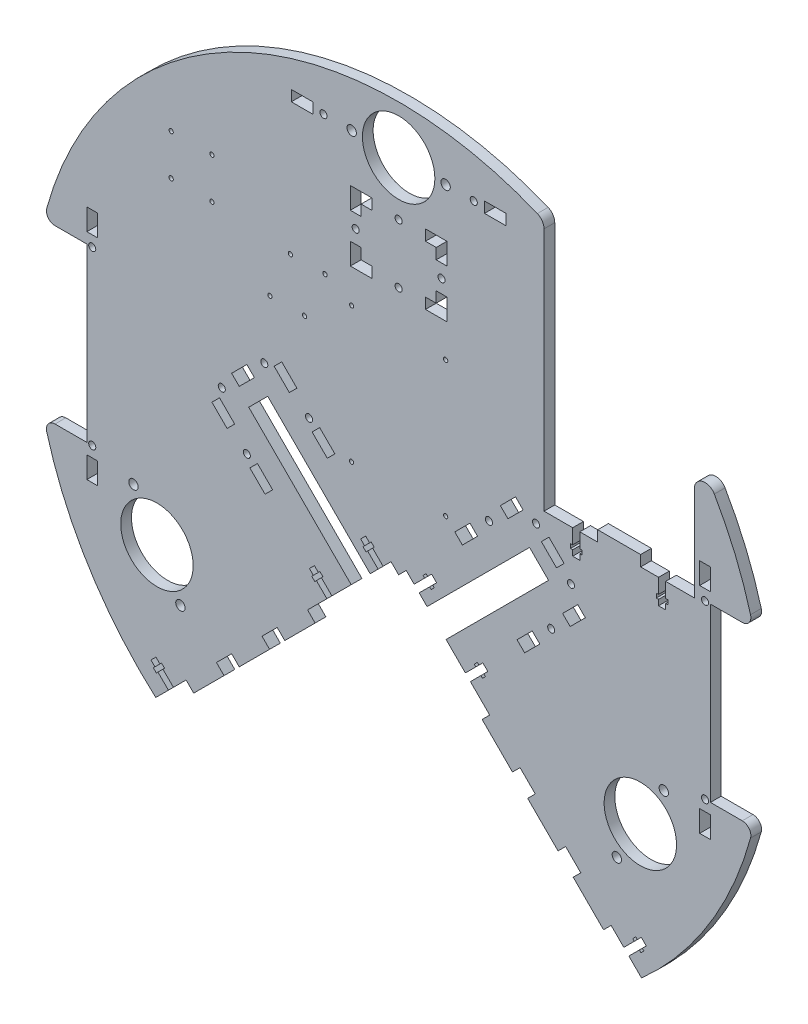
SolidWorks part; units mm, degrees
ref_plane "Front Plane" through (0, 0, 0) normal (0, 0, 1) x (1, 0, 0)
ref_plane "Top Plane" through (0, 0, 0) normal (0, 1, 0) x (1, 0, 0)
ref_plane "Right Plane" through (0, 0, 0) normal (1, 0, 0) x (0, 0, -1)
sketch "Sketch1" plane through (0, 0, 0) normal (0, 0, 1) x (1, 0, 0)
  circle A0 centre (0, 0) radius 215.9
  dimension "D1" = 431.8
extrude "Base Plate Extrusion" add sketch "Sketch1" along normal blind 6.35
sketch "Sketch2" plane through (0, 0, 6.35) normal (0, 0, 1) x (1, 0, 0)
  line L0 (0, 0) -> (0, -230.9791) construction
  line L1 (0, -17.4608) -> (143.6841, -161.1449)
  line L2 (0, -17.4608) -> (-143.6841, -161.1449)
  circle A1 centre (0, 0) radius 215.9 construction
  arc A2 (143.6841, -161.1449) -> (-143.6841, -161.1449) centre (0, 0) cw
  dimension "D1" = 90
  dimension "D2" = 203.2
extrude "V Funnel Cut" cut sketch "Sketch2" against normal through all
sketch "Sketch3" plane through (0, 0, 6.35) normal (0, 0, 1) x (1, 0, 0)
  line L0 (0, 0) -> (251.7982, 0) construction
  line L1 (209.8384, 50.8) -> (184.4384, 50.8)
  line L2 (209.8384, 50.8) -> (209.8384, -50.8)
  line L3 (209.8384, -50.8) -> (184.4384, -50.8)
  line L4 (184.4384, 50.8) -> (184.4384, -50.8)
  arc A0 (143.6841, -161.1449) -> (-143.6841, -161.1449) centre (0, 0) ccw construction
  arc A1 (209.8384, 50.8) -> (209.8384, -50.8) centre (0, 0) cw
  arc M7 (143.6841, -161.1449) -> (-143.6841, -161.1449) centre (0, 0) ccw
  dimension "D1" = 25.4
  dimension "D2" = 101.6
extrude "Wheel Track Cut" cut sketch "Sketch3" against normal through all contours L2 L0 A1 | L4 L0 L2 L1 | L0 L4 L3 L2 | L0 L2 M7 region at (197.1384, 25.4, 6.35) region at (197.1384, -25.4, 6.35) region at (212.266, 19.0862, 6.35) region at (212.266, -19.0862, 6.35)
mirror "Wheel Track Cut Mirror" about plane through (0, 0, 0) normal (1, 0, 0) of "Wheel Track Cut"
sketch "Sketch4" plane through (0, 0, 6.35) normal (0, 0, 1) x (1, 0, 0)
  line L0 (88.68, 15.0926) -> (77.4547, 26.3179)
  line L1 (88.68, 15.0926) -> (28.0633, -45.5241)
  line L2 (77.4547, 26.3179) -> (16.838, -34.2988)
  line L3 (28.0633, -45.5241) -> (16.838, -34.2988)
  line L4 (84.3174, 21.9553) -> (56.956, -5.4061) construction
  line L5 (65.1069, -1.7454) -> (69.5826, 2.7303) construction
  line L6 (65.0924, 7.2204) -> (60.6167, 2.7447) construction
  line L7 (143.6841, -161.1449) -> (0, -17.4608) construction
  dimension "D1" = 15.875
  dimension "D2" = 85.725
extrude "Silo Picker Clearance" cut sketch "Sketch4" against normal through all
sketch "Sketch5" plane through (0, 0, 6.35) normal (0, 0, 1) x (1, 0, 0)
  line L0 (-4.4901, -21.951) -> (0, -17.4608)
  line L1 (-4.4901, -21.951) -> (0, -26.4411)
  line L2 (0, -17.4608) -> (4.4901, -21.951)
  line L3 (0, -26.4411) -> (4.4901, -21.951)
  line L4 (0, -17.4608) -> (-143.6841, -161.1449) construction
  line L6 (4.4901, -21.951) -> (0, -26.4411) construction
  dimension "D1" = 6.35
extrude "V Funnel Corner" add sketch "Sketch5" against normal up to surface (6.35 mm away) up to face at (14.0691, -14.8765, 0)
mirror "Dump Picker Clearance" about plane through (0, 0, 0) normal (1, 0, 0) of "Silo Picker Clearance"
sketch "Sketch6" plane through (8.7304, -8.7304, 0) normal (0.7071, -0.7071, 0) x (0, 0, -1)
  line L0 (-6.35, -52.0342) -> (-6.35, -215.5467) construction
  line L1 (-6.35, -190.1467) -> (0, -190.1467)
  line L2 (-6.35, -190.1467) -> (-6.35, -164.7467)
  line L3 (-6.35, -164.7467) -> (0, -164.7467)
  line L4 (0, -190.1467) -> (0, -164.7467)
  line L5 (0, -52.0342) -> (0, -215.5467) construction
  dimension "D1" = 25.4
  dimension "D2" = 25.4
extrude "V Funnel Tab Left" add sketch "Sketch6" along normal blind 6.35
pattern_linear "V Funnel Tab Pattern Left" count 3 spacing 38.1 along (0.7071, 0.7071, 0) of "V Funnel Tab Left"
sketch "Sketch7" plane through (-8.7304, -8.7304, 0) normal (-0.7071, -0.7071, 0) x (0, 0, 1)
  line L0 (6.35, -215.5467) -> (6.35, -52.0342) construction
  line L1 (6.35, -164.7467) -> (0, -164.7467)
  line L2 (6.35, -164.7467) -> (6.35, -190.1467)
  line L3 (6.35, -190.1467) -> (0, -190.1467)
  line L4 (0, -164.7467) -> (0, -190.1467)
  line L5 (0, -215.5467) -> (0, -52.0342) construction
  dimension "D1" = 25.4
  dimension "D2" = 25.4
extrude "V Funnel Tab Right" add sketch "Sketch7" along normal blind 6.35
pattern_linear "V Funnel Tab Pattern Right" count 3 spacing 38.1 along (-0.7071, 0.7071, 0) of "V Funnel Tab Right"
sketch "Sketch8" plane through (0, 0, 0) normal (0, 0, -1) x (-1, 0, 0)
  line L0 (-70.046, -24.645) -> (-79.0263, -15.6648)
  line L1 (-79.0263, -15.6648) -> (-83.5164, -20.1549)
  line L2 (-83.5164, -20.1549) -> (-74.5361, -29.1352)
  line L3 (-74.5361, -29.1352) -> (-70.046, -24.645)
  line L4 (-96.9868, 2.2957) -> (-101.4769, -2.1944)
  line L5 (-101.4769, -2.1944) -> (-110.4572, 6.7859)
  line L6 (-110.4572, 6.7859) -> (-105.967, 11.276)
  line L7 (-105.967, 11.276) -> (-96.9868, 2.2957)
  line L8 (-97.8965, 28.3267) -> (-88.9163, 37.307)
  line L9 (-88.9163, 37.307) -> (-84.4262, 32.8169)
  line L10 (-84.4262, 32.8169) -> (-93.4064, 23.8366)
  line L11 (-93.4064, 23.8366) -> (-97.8965, 28.3267)
  line L12 (-64.6578, 34.6246) -> (-60.1677, 39.1148)
  line L13 (-60.1677, 39.1148) -> (-69.148, 48.095)
  line L14 (-69.148, 48.095) -> (-73.6381, 43.6049)
  line L15 (-73.6381, 43.6049) -> (-64.6578, 34.6246)
  line L16 (-46.6973, 16.6641) -> (-42.2072, 21.1543)
  line L17 (-42.2072, 21.1543) -> (-33.2269, 12.174)
  line L18 (-33.2269, 12.174) -> (-37.7171, 7.6839)
  line L19 (-37.7171, 7.6839) -> (-46.6973, 16.6641)
  line L20 (-105.967, 11.276) -> (-110.4572, 6.7859) construction
  line L21 (-69.148, 48.095) -> (-73.6381, 43.6049) construction
extrude "Silo Arm Tab Holes" cut sketch "Sketch8" against normal blind 6.35
sketch "Sketch10" plane through (0, 0, 0) normal (0, 0, -1) x (-1, 0, 0)
  line L0 (51.1875, 21.1543) -> (42.2072, 12.174)
  line L1 (42.2072, 12.174) -> (37.7171, 16.6641)
  line L2 (37.7171, 16.6641) -> (46.6973, 25.6444)
  line L3 (46.6973, 25.6444) -> (51.1875, 21.1543)
  line L4 (64.6578, 34.6246) -> (60.1677, 39.1148)
  line L5 (60.1677, 39.1148) -> (69.148, 48.095)
  line L6 (69.148, 48.095) -> (73.6381, 43.6049)
  line L7 (73.6381, 43.6049) -> (64.6578, 34.6246)
  line L8 (89.8026, 36.4207) -> (85.3124, 31.9306)
  line L9 (85.3124, 31.9306) -> (94.2927, 22.9503)
  line L10 (94.2927, 22.9503) -> (98.7828, 27.4404)
  line L11 (98.7828, 27.4404) -> (89.8026, 36.4207)
  line L12 (105.967, 11.276) -> (96.9868, 2.2957)
  line L13 (96.9868, 2.2957) -> (101.4769, -2.1944)
  line L14 (101.4769, -2.1944) -> (110.4572, 6.7859)
  line L15 (110.4572, 6.7859) -> (105.967, 11.276)
  line L16 (88.0065, -15.6648) -> (83.5164, -11.1747)
  line L17 (83.5164, -11.1747) -> (74.5361, -20.1549)
  line L18 (74.5361, -20.1549) -> (79.0263, -24.645)
  line L19 (79.0263, -24.645) -> (88.0065, -15.6648)
  line L20 (37.7171, 16.6641) -> (42.2072, 12.174) construction
  line L21 (74.5361, -20.1549) -> (79.0263, -24.645) construction
extrude "Dump Arm Tab Holes" cut sketch "Sketch10" against normal blind 6.35
sketch "Sketch11" plane through (0, 0, 0) normal (0, 0, -1) x (-1, 0, 0)
  line L1 (184.4384, -69.85) -> (178.0884, -69.85)
  line L2 (184.4384, -69.85) -> (184.4384, -57.15)
  line L3 (184.4384, -57.15) -> (178.0884, -57.15)
  line L4 (178.0884, -69.85) -> (178.0884, -57.15)
  line L5 (184.4384, 57.15) -> (178.0884, 57.15)
  line L6 (184.4384, 57.15) -> (184.4384, 69.85)
  line L7 (184.4384, 69.85) -> (178.0884, 69.85)
  line L8 (178.0884, 57.15) -> (178.0884, 69.85)
  line L9 (-178.0884, -69.85) -> (-184.4384, -69.85)
  line L10 (-178.0884, -69.85) -> (-178.0884, -57.15)
  line L11 (-178.0884, -57.15) -> (-184.4384, -57.15)
  line L12 (-184.4384, -69.85) -> (-184.4384, -57.15)
  line L13 (-178.0884, 57.15) -> (-184.4384, 57.15)
  line L14 (-178.0884, 57.15) -> (-178.0884, 69.85)
  line L15 (-178.0884, 69.85) -> (-184.4384, 69.85)
  line L16 (-184.4384, 57.15) -> (-184.4384, 69.85)
extrude "Wheel Support Tab Holes" cut sketch "Sketch11" against normal blind 6.35
sketch "Sketch13" plane through (0, 0, 6.35) normal (0, 0, 1) x (1, 0, 0)
  circle A0 centre (0, 187.325) radius 21.4313
  circle A1 centre (27.7812, 187.325) radius 2.7781
  circle A2 centre (-27.7813, 187.325) radius 2.7781
  dimension "D1" = 42.8625
  dimension "D2" = 5.5562
extrude "Caster Wheel Hole" cut sketch "Sketch13" against normal through all
sketch "Sketch14" plane through (0, 0, 6.35) normal (0, 0, 1) x (1, 0, 0)
  line L0 (184.4384, 48.6664) -> (178.0884, 52.9336) construction
  line L1 (184.4384, 50.8) -> (184.4384, -50.8) construction
  line L2 (178.0884, 48.6664) -> (184.4384, 48.6664) construction
  line L3 (184.4384, 52.9336) -> (178.0884, 48.6664) construction
  line L4 (184.4384, -52.9336) -> (178.0884, -48.6664) construction
  line L5 (184.4384, -48.6664) -> (178.0884, -52.9336) construction
  line L6 (178.0884, -48.6664) -> (184.4384, -48.6664) construction
  circle A0 centre (181.2634, 50.8) radius 2.0955
  circle A1 centre (181.2634, -50.8) radius 2.0955
  dimension "D1" = 4.191
extrude "Wheel Support Hole" cut sketch "Sketch14" against normal through all
mirror "Wheel Support Hole Mirror" about plane through (0, 0, 0) normal (1, 0, 0) of "Wheel Support Hole"
sketch "Sketch15" plane through (0, 0, 6.35) normal (0, 0, 1) x (1, 0, 0)
  line L0 (-134.7038, -152.1647) -> (-152.6084, -134.2601) construction
  line L1 (-125.7236, -143.1844) -> (-143.6841, -161.1449) construction
  line L2 (-40.9724, -58.4333) -> (-60.7132, -38.6924) construction
  line L3 (-28.0633, -45.5241) -> (-53.8815, -71.3424) construction
  line L4 (-10.6641, -28.1249) -> (-27.2834, -11.5055) construction
  line L5 (-4.4901, -21.951) -> (-16.838, -34.2988) construction
  line B0 (-136.1856, -153.6464) -> (-133.2221, -150.6829)
  line B1 (-141.2145, -142.6905) -> (-140.2716, -141.7476)
  line B2 (-140.2716, -141.7476) -> (-138.4755, -143.5436)
  line B3 (-138.4755, -143.5436) -> (-139.4185, -144.4866)
  line B4 (-139.4185, -144.4866) -> (-133.2221, -150.6829)
  line B5 (-141.2145, -142.6905) -> (-143.5494, -140.3556)
  line B6 (-143.5494, -140.3556) -> (-146.5129, -143.3191)
  line B7 (-144.178, -145.654) -> (-146.5129, -143.3191)
  line B8 (-142.382, -147.45) -> (-136.1856, -153.6464)
  line B9 (-143.3249, -148.393) -> (-142.382, -147.45)
  line B10 (-145.1209, -146.5969) -> (-143.3249, -148.393)
  line B11 (-144.178, -145.654) -> (-145.1209, -146.5969)
  line B12 (-42.4542, -59.915) -> (-39.4907, -56.9515)
  line B13 (-47.4831, -48.9591) -> (-46.5402, -48.0162)
  line B14 (-46.5402, -48.0162) -> (-44.7441, -49.8122)
  line B15 (-44.7441, -49.8122) -> (-45.6871, -50.7551)
  line B16 (-45.6871, -50.7551) -> (-39.4907, -56.9515)
  line B17 (-47.4831, -48.9591) -> (-49.818, -46.6242)
  line B18 (-49.818, -46.6242) -> (-52.7815, -49.5877)
  line B19 (-50.4466, -51.9226) -> (-52.7815, -49.5877)
  line B20 (-48.6505, -53.7186) -> (-42.4542, -59.915)
  line B21 (-49.5935, -54.6615) -> (-48.6505, -53.7186)
  line B22 (-51.3895, -52.8655) -> (-49.5935, -54.6615)
  line B23 (-50.4466, -51.9226) -> (-51.3895, -52.8655)
  line B24 (-12.1458, -29.6066) -> (-9.1823, -26.6431)
  line B25 (-17.1747, -18.6507) -> (-16.2318, -17.7078)
  line B26 (-16.2318, -17.7078) -> (-14.4358, -19.5038)
  line B27 (-14.4358, -19.5038) -> (-15.3787, -20.4468)
  line B28 (-15.3787, -20.4468) -> (-9.1823, -26.6431)
  line B29 (-17.1747, -18.6507) -> (-19.5096, -16.3159)
  line B30 (-19.5096, -16.3159) -> (-22.4731, -19.2793)
  line B31 (-20.1382, -21.6142) -> (-22.4731, -19.2793)
  line B32 (-18.3422, -23.4103) -> (-12.1458, -29.6066)
  line B33 (-19.2851, -24.3532) -> (-18.3422, -23.4103)
  line B34 (-21.0812, -22.5571) -> (-19.2851, -24.3532)
  line B35 (-20.1382, -21.6142) -> (-21.0812, -22.5571)
sketch_block_instance "TSlot-1"
sketch_block "TSlot" parameters "D1"=3.302, "D2"=2.54, "D3"=3.175, "D4"=8.763, "D5"=1.3462
sketch_block_instance "TSlot-3"
sketch_block_instance "TSlot-4"
extrude "V Funnel T Slot Cut Out" cut sketch "Sketch15" against normal through all
mirror "V Funnel T Slot Cut Out Mirror" about plane through (0, 0, 0) normal (1, 0, 0) of "V Funnel T Slot Cut Out"
sketch "Sketch19" plane through (0, 0, 6.35) normal (0, 0, 1) x (1, 0, 0)
  line L0 (46.5836, 190.5) -> (42.3164, 184.15) construction
  line L1 (46.5836, 184.15) -> (42.3164, 190.5) construction
  line L2 (-42.3164, 190.5) -> (-46.5836, 184.15) construction
  line L3 (-42.3164, 184.15) -> (-46.5836, 190.5) construction
  circle A0 centre (44.45, 187.325) radius 2.0955
  circle A1 centre (-44.45, 187.325) radius 2.0955
  dimension "D1" = 4.191
extrude "Switch Plate Holes" cut sketch "Sketch19" against normal through all
sketch "Sketch20" plane through (0, 0, 0) normal (0, 0, -1) x (-1, 0, 0)
  line L1 (-50.8, 184.15) -> (-63.5, 184.15)
  line L2 (-50.8, 184.15) -> (-50.8, 190.5)
  line L3 (-50.8, 190.5) -> (-63.5, 190.5)
  line L4 (-63.5, 184.15) -> (-63.5, 190.5)
  line L5 (63.5, 184.15) -> (50.8, 184.15)
  line L6 (63.5, 184.15) -> (63.5, 190.5)
  line L7 (63.5, 190.5) -> (50.8, 190.5)
  line L8 (50.8, 184.15) -> (50.8, 190.5)
extrude "Swith Plate Tab Holes" cut sketch "Sketch20" against normal through all
sketch "Sketch26" plane through (0, 0, 6.35) normal (0, 0, 1) x (1, 0, 0)
  line L0 (89.5152, -5.1758) -> (90.988, -12.6833) construction
  line L1 (86.4978, -8.1932) -> (94.0053, -9.666) construction
  line L2 (52.6961, 31.6432) -> (54.1689, 24.1357) construction
  line L3 (49.6788, 28.6258) -> (57.1863, 27.1531) construction
  line L4 (105.6855, 20.5377) -> (98.178, 19.065) construction
  line L5 (102.6682, 23.5551) -> (101.1954, 16.0476) construction
  line L6 (82.0136, 44.2097) -> (80.5408, 36.7022) construction
  line L7 (85.0309, 41.1923) -> (77.5234, 39.7196) construction
  circle A0 centre (90.2516, -8.9296) radius 2.0955
  circle A1 centre (53.4325, 27.8895) radius 2.0955
  circle A2 centre (101.9318, 19.8014) radius 2.0955
  circle A3 centre (81.2772, 40.4559) radius 2.0955
  dimension "D1" = 4.191
extrude "Silo Arm Holes" cut sketch "Sketch26" against normal through all
sketch "Sketch27" plane through (0, 0, 6.35) normal (0, 0, 1) x (1, 0, 0)
  line L0 (-49.2298, 28.1768) -> (-56.7373, 26.7041) construction
  line L1 (-52.2471, 31.1942) -> (-53.7199, 23.6867) construction
  line L2 (-80.2116, 46.0116) -> (-78.7389, 38.5041) construction
  line L3 (-83.229, 42.9942) -> (-75.7215, 41.5215) construction
  line L4 (-105.3564, 20.8669) -> (-103.8836, 13.3594) construction
  line L5 (-108.3737, 17.8495) -> (-100.8662, 16.3768) construction
  line L6 (-93.5563, -10.115) -> (-86.0488, -8.6422) construction
  line L7 (-90.5389, -13.1324) -> (-89.0662, -5.6249) construction
  circle A0 centre (-52.9835, 27.4404) radius 2.0955
  circle A1 centre (-79.4753, 42.2579) radius 2.0955
  circle A2 centre (-104.62, 17.1131) radius 2.0955
  circle A3 centre (-89.8026, -9.3786) radius 2.0955
  dimension "D1" = 4.191
extrude "Dump Arm Holes" cut sketch "Sketch27" against normal through all
fillet "Wheel Slot Fillet" radius 5.08 4 edges at (209.8384, -50.8, 3.175) (209.8384, 50.8, 3.175) (-209.8384, -50.8, 3.175) (-209.8384, 50.8, 3.175)
sketch "Sketch28" plane through (0, 0, 6.35) normal (0, 0, 1) x (1, 0, 0)
  line L0 (0, 0) -> (0, 258.9974) construction
  line L1 (0, 0) -> (249.4479, -144.0188) construction
  line L2 (0, 0) -> (-249.719, -144.1753) construction
  line L3 (-142.9808, -82.55) -> (-156.8714, -58.4907) construction
  line L4 (-27.7813, 187.325) -> (0, 187.325) construction
  line L5 (-142.9808, -82.55) -> (-129.0902, -106.6093) construction
  circle A0 centre (-142.9808, -82.55) radius 21.4313
  circle A1 centre (0, 187.325) radius 21.4313 construction
  circle A2 centre (-156.8714, -58.4907) radius 2.7781
  circle A3 centre (-27.7813, 187.325) radius 2.7781 construction
  circle A4 centre (-129.0902, -106.6093) radius 2.7781
  dimension "D1" = 120
  dimension "D2" = 120
  dimension "D3" = 165.1
extrude "Front Caster Holes" cut sketch "Sketch28" against normal through all
mirror "Front Caster Hole Mirror" about plane through (0, 0, 0) normal (1, 0, 0) of "Front Caster Holes"
sketch "Gyro Holes" plane through (0, 0, 6.35) normal (0, 0, 1) x (1, 0, 0)
  line L1 (-134.5682, 109.4626) -> (-110.4382, 109.4626) construction
  line L2 (-134.5682, 109.4626) -> (-134.5682, 133.5926) construction
  line L3 (-134.5682, 133.5926) -> (-110.4382, 133.5926) construction
  line L4 (-110.4382, 109.4626) -> (-110.4382, 133.5926) construction
  line L5 (-134.5682, 109.4626) -> (-110.4382, 133.5926) construction
  line L6 (-134.5682, 133.5926) -> (-110.4382, 109.4626) construction
  circle A0 centre (-134.5682, 133.5926) radius 1.27
  circle A1 centre (-110.4382, 133.5926) radius 1.27
  circle A2 centre (-110.4382, 109.4626) radius 1.27
  circle A3 centre (-134.5682, 109.4626) radius 1.27
  point P0 (-122.5032, 121.5276)
  dimension "D2" = 24.13
  dimension "D1" = 2.54
extrude "GyroHoles" cut sketch "Gyro Holes" against normal through all
sketch "MotorControllerHoleSketch" plane through (0, 0, 6.35) normal (0, 0, 1) x (1, 0, 0)
  line L0 (0, 215.9) -> (0, -26.4411) construction
  line L2 (-27.82, 17.5746) -> (27.82, 17.5746) construction
  line L3 (-27.82, 17.5746) -> (-27.82, 97.6146) construction
  line L4 (-27.82, 97.6146) -> (27.82, 97.6146) construction
  line L5 (27.82, 17.5746) -> (27.82, 97.6146) construction
  line L6 (-27.82, 17.5746) -> (27.82, 97.6146) construction
  line L7 (-27.82, 97.6146) -> (27.82, 17.5746) construction
  arc A0 (208.1777, 57.2265) -> (-208.1777, 57.2265) centre (0, 0) ccw construction
  circle A1 centre (-27.82, 97.6146) radius 1.25
  circle A2 centre (27.82, 97.6146) radius 1.25
  circle A3 centre (27.82, 17.5746) radius 1.25
  circle A4 centre (-27.82, 17.5746) radius 1.25
  point P6 (0, 57.5946)
  dimension "D1" = 2.5
  dimension "D2" = 55.64
  dimension "D3" = 80.04
extrude "Motor Controller Hole" cut sketch "MotorControllerHoleSketch" against normal through all
sketch "Sketch31" plane through (0, 0, 6.35) normal (0, 0, 1) x (1, 0, 0)
  line L0 (-59.8452, 118.6025) -> (-59.8452, 61.2016) construction
  line L1 (-43.5402, 78.4228) -> (-55.6734, 78.4228) construction
  line L2 (-43.5402, 78.4228) -> (-43.5402, 105.8377) construction
  line L3 (-43.5402, 105.8377) -> (-55.6734, 105.8377) construction
  line L4 (-55.6734, 78.4228) -> (-55.6734, 105.8377) construction
  line L5 (-43.5402, 78.4228) -> (-55.6734, 105.8377) construction
  line L6 (-43.5402, 105.8377) -> (-55.6734, 78.4228) construction
  line L7 (-64.017, 78.4228) -> (-76.1502, 78.4228) construction
  line L8 (-64.017, 78.4228) -> (-64.017, 105.8377) construction
  line L9 (-64.017, 105.8377) -> (-76.1502, 105.8377) construction
  line L10 (-76.1502, 78.4228) -> (-76.1502, 105.8377) construction
  line L11 (-64.017, 78.4228) -> (-76.1502, 105.8377) construction
  line L12 (-64.017, 105.8377) -> (-76.1502, 78.4228) construction
  line L13 (-70.0836, 92.1303) -> (-49.6068, 92.1303) construction
  circle A0 centre (-76.1502, 78.4228) radius 1.27
  circle A1 centre (-64.017, 105.8377) radius 1.27
  circle A2 centre (-55.6734, 78.4228) radius 1.27
  circle A3 centre (-43.5402, 105.8377) radius 1.27
  point P0 (-49.6068, 92.1303)
  point P5 (-70.0836, 92.1303)
  dimension "D1" = 2.54
extrude "BuckConverterHoles" cut sketch "Sketch31" against normal through all
sketch "Sketch34" plane through (0, 0, 0) normal (0, 0, -1) x (-1, 0, 0)
  line L1 (-28.575, 158.75) -> (-15.875, 158.75)
  line L2 (-28.575, 158.75) -> (-28.575, 152.4)
  line L3 (-22.225, 152.4) -> (-15.875, 152.4)
  line L4 (-15.875, 158.75) -> (-15.875, 152.4)
  line L5 (15.875, 158.75) -> (28.575, 158.75)
  line L6 (15.875, 158.75) -> (15.875, 152.4)
  line L7 (15.875, 152.4) -> (22.225, 152.4)
  line L8 (28.575, 158.75) -> (28.575, 152.4)
  line L9 (15.875, 123.825) -> (22.225, 123.825)
  line L10 (15.875, 123.825) -> (15.875, 117.475)
  line L11 (15.875, 117.475) -> (28.575, 117.475)
  line L12 (28.575, 123.825) -> (28.575, 117.475)
  line L13 (-22.225, 123.825) -> (-15.875, 123.825)
  line L14 (-28.575, 123.825) -> (-28.575, 117.475)
  line L15 (-28.575, 117.475) -> (-15.875, 117.475)
  line L16 (-15.875, 123.825) -> (-15.875, 117.475)
  line L17 (-28.575, 130.175) -> (-22.225, 130.175)
  line L18 (-28.575, 130.175) -> (-28.575, 123.825)
  line L20 (-22.225, 130.175) -> (-22.225, 123.825)
  line L22 (-28.575, 152.4) -> (-28.575, 146.05)
  line L23 (-28.575, 146.05) -> (-22.225, 146.05)
  line L24 (-22.225, 152.4) -> (-22.225, 146.05)
  line L26 (22.225, 152.4) -> (22.225, 146.05)
  line L27 (22.225, 146.05) -> (28.575, 146.05)
  line L28 (28.575, 152.4) -> (28.575, 146.05)
  line L29 (22.225, 130.175) -> (28.575, 130.175)
  line L30 (22.225, 130.175) -> (22.225, 123.825)
  line L32 (28.575, 130.175) -> (28.575, 123.825)
extrude "Cut-Extrude6" cut sketch "Sketch34" against normal through all
sketch "Sketch35" plane through (0, 0, 6.35) normal (0, 0, 1) x (1, 0, 0)
  line L0 (-22.225, 136.017) -> (-28.575, 140.208) construction
  line L1 (-28.575, 136.017) -> (-22.225, 140.208) construction
  line L2 (-2.0955, 152.4) -> (2.0955, 158.75) construction
  line L3 (2.0955, 152.4) -> (-2.0955, 158.75) construction
  line L4 (22.225, 136.017) -> (28.575, 140.208) construction
  line L5 (22.225, 140.208) -> (28.575, 136.017) construction
  line L6 (2.0955, 123.825) -> (-2.0955, 117.475) construction
  line L7 (-2.0955, 123.825) -> (2.0955, 117.475) construction
  circle A0 centre (0, 120.65) radius 2.0955
  circle A1 centre (25.4, 138.1125) radius 2.0955
  circle A2 centre (0, 155.575) radius 2.0955
  circle A3 centre (-25.4, 138.1125) radius 2.0955
  dimension "D1" = 4.191
extrude "Cut-Extrude7" cut sketch "Sketch35" against normal through all
sketch "Sketch36" plane through (0, 0, 6.35) normal (0, 0, 1) x (1, 0, 0)
  line L0 (86.0134, 198.0265) -> (86.0134, 49.1901)
  line L1 (86.0134, 49.1901) -> (174.9134, 49.1901)
  line L2 (174.9134, 49.1901) -> (174.9134, 126.5626)
  line L3 (174.9134, 105.1417) -> (174.9134, 49.1901) construction
  line L4 (86.0134, 49.1901) -> (86.0134, 193.8168) construction
  arc A0 (208.1777, 57.2265) -> (-208.1777, 57.2265) centre (0, 0) ccw construction
  arc A1 (86.0134, 198.0265) -> (174.9134, 126.5626) centre (0, 0) cw
extrude "Cut-Extrude8" cut sketch "Sketch36" against normal through all
sketch "Sketch37" plane through (0, 0, 0) normal (0, 0, -1) x (-1, 0, 0)
  line L0 (-86.0134, 49.1901) -> (-174.9134, 49.1901) construction
  line L1 (-117.7634, 49.1901) -> (-143.1634, 49.1901)
  line L2 (-117.7634, 49.1901) -> (-117.7634, 55.5401)
  line L3 (-117.7634, 55.5401) -> (-143.1634, 55.5401)
  line L4 (-143.1634, 49.1901) -> (-143.1634, 55.5401)
  line L5 (-117.7634, 49.1901) -> (-117.7634, 55.5401) construction
extrude "Boss-Extrude1" add sketch "Sketch37" against normal up to surface (6.35 mm away) up to face at (3.9427, -63.0423, 6.35)
sketch "Sketch38" plane through (0, 0, 0) normal (0, 0, -1) x (-1, 0, 0)
  line L2 (-86.0134, 49.1901) -> (-174.9134, 49.1901) construction
  line L4 (-143.1634, 55.5401) -> (-143.1634, 49.1901) construction
  line L5 (-168.5634, 131.7401) -> (-168.5634, 55.5401) construction
  line L7 (-92.3634, 55.5401) -> (-92.3634, 131.7401) construction
  line L8 (-117.7634, 49.1901) -> (-117.7634, 55.5401) construction
  line B0 (-102.9679, 49.1901) -> (-107.1589, 49.1901)
  line B1 (-107.1589, 37.8871) -> (-108.4924, 37.8871)
  line B2 (-108.4924, 37.8871) -> (-108.4924, 40.4271)
  line B3 (-108.4924, 40.4271) -> (-107.1589, 40.4271)
  line B4 (-107.1589, 40.4271) -> (-107.1589, 49.1901)
  line B5 (-107.1589, 37.8871) -> (-107.1589, 34.5851)
  line B6 (-107.1589, 34.5851) -> (-102.9679, 34.5851)
  line B7 (-102.9679, 37.8871) -> (-102.9679, 34.5851)
  line B8 (-102.9679, 40.4271) -> (-102.9679, 49.1901)
  line B9 (-101.6344, 40.4271) -> (-102.9679, 40.4271)
  line B10 (-101.6344, 37.8871) -> (-101.6344, 40.4271)
  line B11 (-102.9679, 37.8871) -> (-101.6344, 37.8871)
  line B12 (-105.0634, 49.1901) -> (-105.0634, 34.5851) construction
  line B13 (-153.7679, 49.1901) -> (-157.9589, 49.1901)
  line B14 (-157.9589, 37.8871) -> (-159.2924, 37.8871)
  line B15 (-159.2924, 37.8871) -> (-159.2924, 40.4271)
  line B16 (-159.2924, 40.4271) -> (-157.9589, 40.4271)
  line B17 (-157.9589, 40.4271) -> (-157.9589, 49.1901)
  line B18 (-157.9589, 37.8871) -> (-157.9589, 34.5851)
  line B19 (-157.9589, 34.5851) -> (-153.7679, 34.5851)
  line B20 (-153.7679, 37.8871) -> (-153.7679, 34.5851)
  line B21 (-153.7679, 40.4271) -> (-153.7679, 49.1901)
  line B22 (-152.4344, 40.4271) -> (-153.7679, 40.4271)
  line B23 (-152.4344, 37.8871) -> (-152.4344, 40.4271)
  line B24 (-153.7679, 37.8871) -> (-152.4344, 37.8871)
  line B25 (-155.8634, 49.1901) -> (-155.8634, 34.5851) construction
sketch_block_instance "TSlot-5"
sketch_block_instance "TSlot-6"
extrude "Cut-Extrude9" cut sketch "Sketch38" against normal through all
fillet "Fillet1" radius 6.35 2 edges at (86.0134, 198.0265, 3.175) (174.9134, 126.5626, 3.175)
